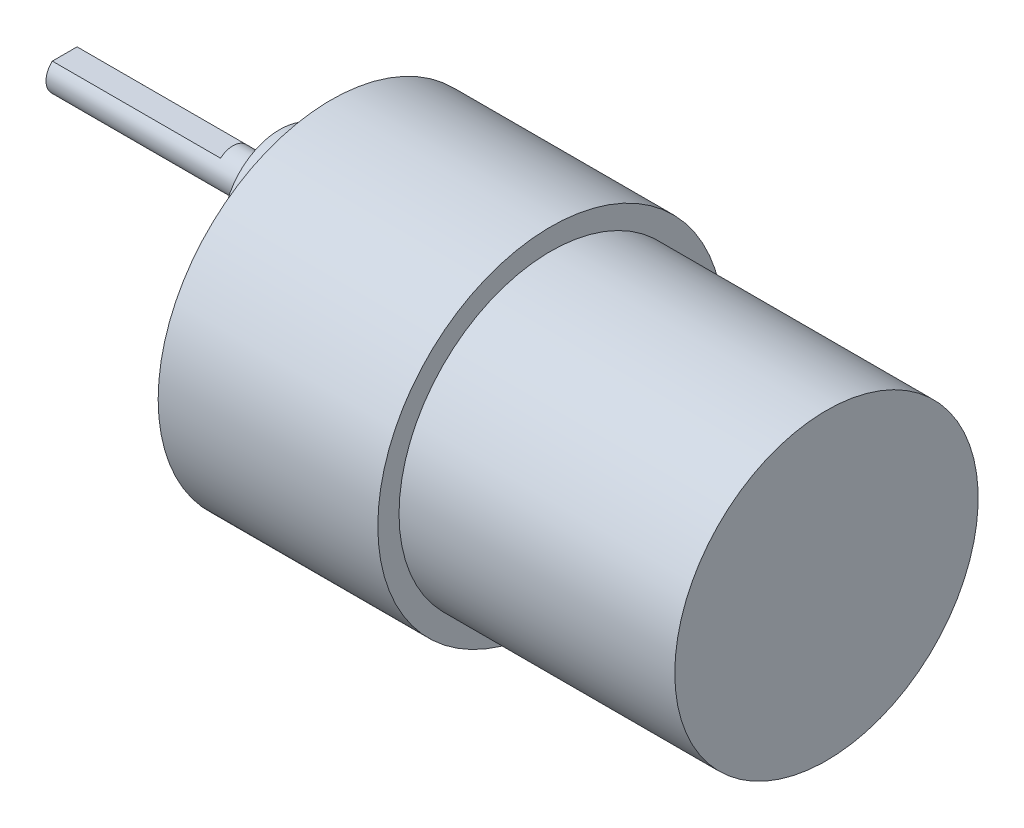
SolidWorks part; units mm, degrees
ref_plane "Front Plane" through (0, 0, 0) normal (0, 0, 1) x (1, 0, 0)
ref_plane "Top Plane" through (0, 0, 0) normal (0, 1, 0) x (1, 0, 0)
ref_plane "Right Plane" through (0, 0, 0) normal (1, 0, 0) x (0, 0, -1)
sketch "Sketch1" plane through (0, 0, 0) normal (0, 0, 1) x (1, 0, 0)
  line L1 (0, 0) -> (23.5, 0)
  line L2 (0, 0) -> (0, 18.5)
  line L3 (0, 18.5) -> (23.5, 18.5)
  line L4 (23.5, 0) -> (23.5, 18.5)
  line L5 (23.5, 16.23) -> (53, 16.23)
  line L6 (23.5, 16.23) -> (23.5, 0)
  line L7 (23.5, 0) -> (53, 0)
  line L8 (53, 16.23) -> (53, 0)
  dimension "D1" = 23.5
  dimension "D2" = 29.5
  dimension "D3" = 16.23
  dimension "D4" = 18.5
revolve "Revolve1" add sketch "Sketch1" angle 360 about L1 region at (11.75, 9.25, 0) region at (38.25, 8.115, 0)
sketch "Sketch2" plane through (0, 0, 0) normal (-1, 0, 0) x (0, 0, 1)
  line L0 (0, 0) -> (0, 18.5) construction
  line L1 (0, 0) -> (7.75, 13.4234) construction
  circle A0 centre (0, 0) radius 15.5 construction
  circle A1 centre (0, 0) radius 18.5 construction
  point P1 (7.75, 13.4234)
  point P4 (15.5, 0)
  point P7 (7.75, -13.4234)
  point P8 (-7.75, -13.4234)
  point P9 (-15.5, 0)
  point P10 (-7.75, 13.4234)
  point P11 (0, 0)
  dimension "D1" = 31
  dimension "D3" = 30
  dimension "D2" = 6
hole_wizard "M3.5x0.6 Tapped Hole1" positions "Sketch3" profile "Sketch5" tap size "M3.5x0.6" standard "ANSI Metric"
sketch "Sketch3" plane through (0, 0, 0) normal (-1, 0, 0) x (0, 0, 1)
  point P0 (7.75, 13.4234)
  point P3 (15.5, 0)
  point P6 (7.75, -13.4234)
  point P9 (-7.75, -13.4234)
  point P12 (-15.5, 0)
  point P15 (-7.75, 13.4234)
sketch "Sketch5" plane through (0, 13.4234, 7.75) normal (0, 1, 0) x (0, 0, 1)
  line L0 (0, 0) -> (0, 4.3712)
  line L1 (0, 4.3712) -> (1.45, 3.5)
  line L2 (1.45, 3.5) -> (1.45, 0)
  line L5 (1.45, 0) -> (0, 0)
  line L10 (0, 4.3712) -> (-1.45, 3.5) construction
  line L11 (0, -6.35) -> (0, 107.95) construction
  dimension "Tap Drill Dia." = 2.9
  dimension "Tap Drill Depth" = 3.5
  dimension "Drill Angle" = 118
cosmetic thread "Hole Thread1" parameters "D1"=7, "D2"=3.5
cosmetic thread "Hole Thread2" parameters "D1"=7, "D2"=3.5
cosmetic thread "Hole Thread3" parameters "D1"=7, "D2"=3.5
cosmetic thread "Hole Thread4" parameters "D1"=7, "D2"=3.5
cosmetic thread "Hole Thread5" parameters "D1"=7, "D2"=3.5
cosmetic thread "Hole Thread6" parameters "D1"=7, "D2"=3.5
sketch "Sketch6" plane through (0, 0, 0) normal (-1, 0, 0) x (0, 0, 1)
  circle A0 centre (0, 7) radius 6
  dimension "D2" = 12
  dimension "D1" = 7
extrude "Boss-Extrude1" add sketch "Sketch6" along normal blind 5.5
sketch "Sketch7" plane through (-5.5, 0, 0) normal (-1, 0, 0) x (0, 0, 1)
  circle A0 centre (0, 7) radius 2
  dimension "D1" = 4
extrude "Boss-Extrude2" add sketch "Sketch7" along normal blind 23
sketch "Sketch8" plane through (-28.5, 0, 0) normal (-1, 0, 0) x (0, 0, 1)
  line L0 (-1.3229, 8.5) -> (1.3229, 8.5)
  circle A0 centre (0, 7) radius 2 construction
  circle A1 centre (0, 7) radius 2
  circle M2 centre (0, 7) radius 2
  dimension "D1" = 3.5
extrude "Cut-Extrude1" cut sketch "Sketch8" against normal blind 18 contours L0 M2 region at (-28.5, 8.7023, 0)
